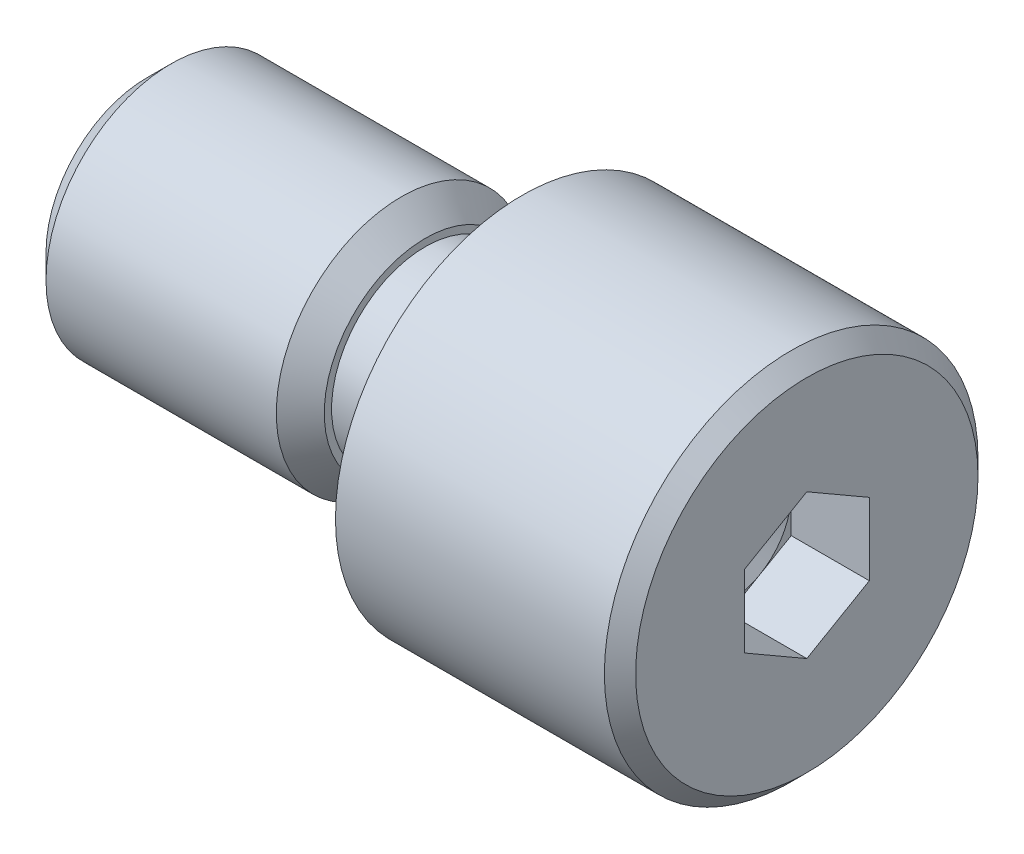
SolidWorks part; units mm, degrees
material "AISI 4130 Steel, normalized at 870C"
ref_plane "X-Y Datum" through (0, 0, 0) normal (0, 0, 1) x (1, 0, 0)
ref_plane "X-Z Datum" through (0, 0, 0) normal (0, 1, 0) x (1, 0, 0)
ref_plane "Y-Z Datum" through (0, 0, 0) normal (1, 0, 0) x (0, 0, -1)
sketch "Sketch1" plane through (0, 0, 0) normal (0, 0, 1) x (1, 0, 0)
  line L0 (0, 4) -> (0, 0)
  line L1 (0, 0) -> (21.1, 0)
  line L2 (21.1, 0) -> (21.1, 5.975)
  line L3 (21.1, 5.975) -> (12, 5.975)
  line L4 (12, 5.975) -> (12, 3)
  line L5 (12, 3) -> (8.9, 3)
  line L6 (8.9, 3) -> (8.9, 4)
  line L7 (8.9, 4) -> (0, 4)
  line L8 (0, 0) -> (21.1, 0) construction
revolve "Revolve1" add sketch "Sketch1" angle 360 about L8 reverse direction yes
sketch "Sketch2" plane through (21.1, 0, 0) normal (1, 0, 0) x (0, 0, -1)
  line L0 (0, -2.3094) -> (2, -1.1547)
  line L1 (2, -1.1547) -> (2, 1.1547)
  line L2 (2, 1.1547) -> (0, 2.3094)
  line L3 (0, 2.3094) -> (-2, 1.1547)
  line L4 (-2, 1.1547) -> (-2, -1.1547)
  line L5 (-2, -1.1547) -> (0, -2.3094)
extrude "Cut-Extrude1" cut sketch "Sketch2" against normal blind 2.5
ref_plane "Plane1" through (0, 0, 0) normal (0, 0, -1) x (-1, 0, 0)
sketch "Sketch3" plane through (0, 0, 0) normal (0, 0, -1) x (-1, 0, 0)
  line L0 (-18.6, 2) -> (-18.6, 0)
  line L1 (-18.6, 0) -> (-17.4453, 0)
  line L2 (-17.4453, 0) -> (-18.6, 2)
  line L3 (-18.6, 0) -> (-17.4453, 0) construction
revolve "Cut-Revolve1" cut sketch "Sketch3" angle 360 about L3 reverse direction yes
chamfer "Chamfer1" distance 0.767 angle 45 2 edges at (0, 0, -4) (8.9, 0, -4)
chamfer "Chamfer2" distance 0.5 angle 45 1 edges at (21.1, 0, -5.975)
fillet "Fillet1" radius 0.2 1 edges at (12, 0, -3) tangent propagation no
move or copy body "Body-Move/Copy1" [suppressed] bodies to move or copy 105 parameters "D1"=0, "D2"=0, "D3"=0
move or copy body "Body-Move/Copy2" [suppressed] bodies to move or copy 106 parameters "D1"=0, "D2"=0, "D3"=0
move or copy body "Body-Move/Copy3" [suppressed] bodies to move or copy 107 parameters "D1"=0, "D2"=0, "D3"=0
move or copy body "Body-Move/Copy4" [suppressed] bodies to move or copy 108 parameters "D1"=0, "D2"=0, "D3"=0
move or copy body "Body-Move/Copy5" [suppressed] bodies to move or copy 109 parameters "D1"=0, "D2"=0, "D3"=0
move or copy body "Body-Move/Copy6" [suppressed] bodies to move or copy 110 parameters "D1"=0, "D2"=0, "D3"=0
move or copy body "Body-Move/Copy7" [suppressed] bodies to move or copy 111 parameters "D1"=0, "D2"=0, "D3"=0
move or copy body "Body-Move/Copy8" [suppressed] bodies to move or copy 112 parameters "D1"=0, "D2"=0, "D3"=0
